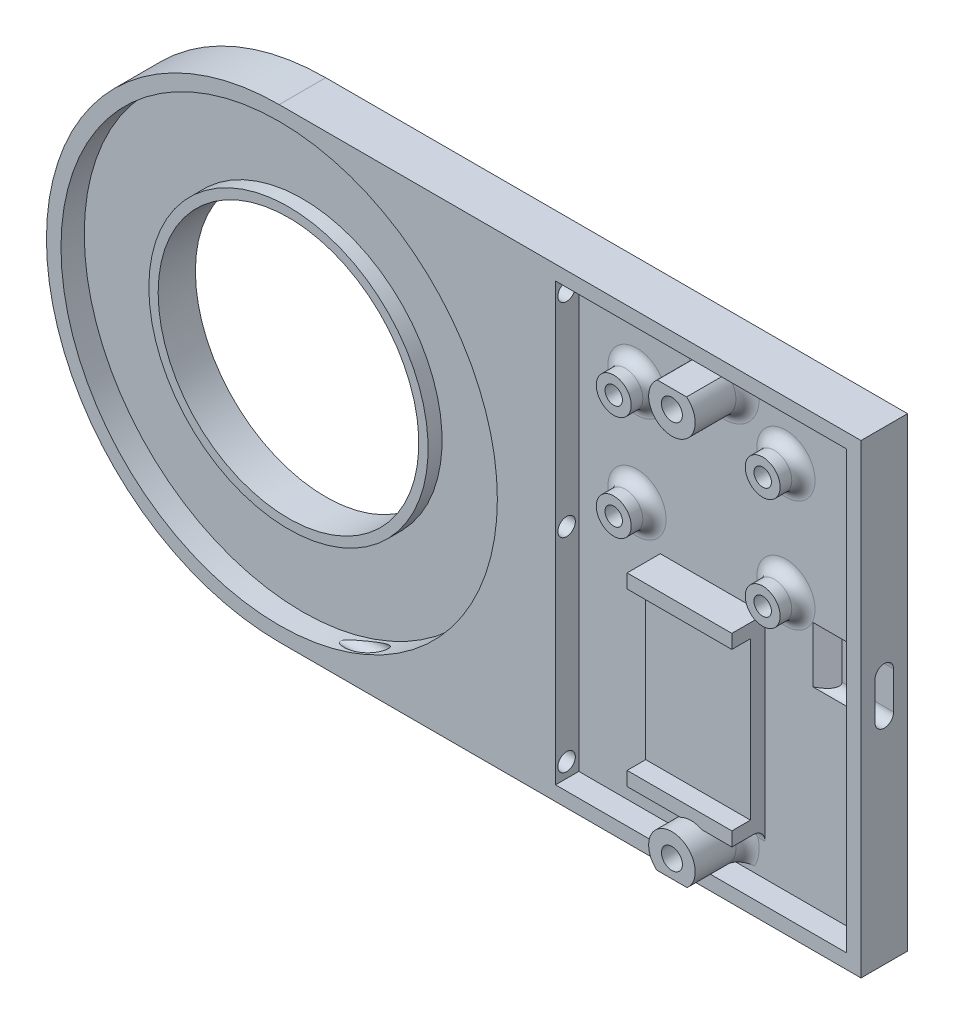
SolidWorks part; units mm, degrees
material "PET"
ref_plane "Front Plane" through (0, 0, 0) normal (0, 0, 1) x (1, 0, 0)
ref_plane "Top Plane" through (0, 0, 0) normal (0, 1, 0) x (1, 0, 0)
ref_plane "Right Plane" through (0, 0, 0) normal (1, 0, 0) x (0, 0, -1)
sketch "Sketch1" plane through (0, 0, 0) normal (0, 0, 1) x (1, 0, 0)
  line L0 (0, 25.4) -> (63.5, 25.4)
  line L1 (63.5, 25.4) -> (63.5, -25.4)
  line L2 (63.5, -25.4) -> (0, -25.4)
  circle A0 centre (0, 0) radius 15.24
  arc A1 (0, 25.4) -> (0, -25.4) centre (0, 0) ccw
  dimension "D1" = 30.48
  dimension "D2" = 25.4
  dimension "D3" = 63.5
extrude "Boss-Extrude1" add sketch "Sketch1" along normal blind 2.54
sketch "Sketch2" plane through (0, 0, 2.54) normal (0, 0, 1) x (1, 0, 0)
  line L3 (63.5, -25.4) -> (63.5, 25.4) construction
  line L4 (0, -25.4) -> (63.5, -25.4) construction
  line L5 (63.5, 25.4) -> (0, 25.4) construction
  line L6 (0, -23.8125) -> (61.9125, -23.8125)
  line L7 (61.9125, -23.8125) -> (61.9125, 23.8125)
  line L8 (61.9125, 23.8125) -> (0, 23.8125)
  line L9 (0, -23.8125) -> (61.9125, -23.8125)
  line L10 (61.9125, -23.8125) -> (61.9125, 23.8125)
  line L11 (61.9125, 23.8125) -> (0, 23.8125)
  line L12 (63.5, -25.4) -> (63.5, 25.4)
  line L13 (0, -25.4) -> (63.5, -25.4)
  line L14 (63.5, 25.4) -> (0, 25.4)
  arc A1 (0, 25.4) -> (0, -25.4) centre (0, 0) ccw construction
  arc A2 (0, 23.8125) -> (0, -23.8125) centre (0, 0) ccw
  arc A3 (0, 23.8125) -> (0, -23.8125) centre (0, 0) ccw
  arc A4 (0, 25.4) -> (0, -25.4) centre (0, 0) ccw
  dimension "D1" = 1.5875
extrude "Boss-Extrude2" add sketch "Sketch2" along normal blind 2.54
sketch "Sketch3" plane through (0, 0, 2.54) normal (0, 0, 1) x (1, 0, 0)
  line L0 (61.9125, 23.8125) -> (0, 23.8125) construction
  line L2 (23.8125, 23.8125) -> (23.8125, -23.8125) construction
  line L4 (30.1625, 23.8125) -> (30.1625, -23.8125)
  line L5 (0, -23.8125) -> (61.9125, -23.8125) construction
  line L6 (23.8125, 0) -> (30.1625, 0) construction
  line L7 (0, -23.8125) -> (30.1625, -23.8125)
  line L8 (0, 23.8125) -> (30.1625, 23.8125)
  circle A1 centre (0, 0) radius 23.8125 construction
  arc A3 (0, -23.8125) -> (0, 23.8125) centre (0, 0) ccw
  dimension "D1" = 6.35
extrude "Boss-Extrude3" add sketch "Sketch3" along normal up to surface (2.54 mm away) contours L4 L7 A3 L8 up to face at (25.4, 0, 5.08)
sketch "Sketch4" plane through (30.1625, 0, 0) normal (1, 0, 0) x (0, 0, -1)
  line L0 (-3.8735, -22.225) -> (-3.8735, 0) construction
  line L1 (-3.8735, 0) -> (-3.8735, 22.225) construction
  line L3 (-5.08, -25.4) -> (0, -25.4) construction
  line L4 (-5.08, 25.4) -> (0, 25.4) construction
  line L5 (-5.08, 0) -> (-4.826, 0) construction
  line L6 (-5.08, -25.4) -> (-5.08, 25.4) construction
  circle A0 centre (-3.8735, 22.225) radius 0.9525
  circle A1 centre (-3.8735, 0) radius 0.9525
  circle A2 centre (-3.8735, -22.225) radius 0.9525
  dimension "D1" = 1.905
  dimension "D2" = 1.905
  dimension "D3" = 1.905
  dimension "D4" = 3.175
  dimension "D5" = 3.175
  dimension "D6" = 25.4
  dimension "D7" = 0.254
extrude "Cut-Extrude1" cut sketch "Sketch4" against normal blind 31.75
sketch "Sketch6" plane through (0, 0, 2.54) normal (0, 0, 1) x (1, 0, 0)
  line L1 (52.7685, 4.3815) -> (36.5125, 4.7625) construction
  line L2 (36.5125, 4.7625) -> (36.5125, 16.1925) construction
  line L3 (36.5125, 16.1925) -> (52.7685, 16.5735) construction
  line L4 (36.5125, 4.7625) -> (52.7685, 4.7625) construction
  line L5 (36.5125, 16.1925) -> (52.7685, 16.1925) construction
  line L6 (52.7685, 16.5735) -> (52.7685, 16.1925) construction
  line L7 (52.7685, 16.1925) -> (52.7685, 4.7625) construction
  line L8 (52.7685, 4.7625) -> (52.7685, 4.3815) construction
  line L10 (30.1625, 23.8125) -> (30.1625, -23.8125) construction
  line L11 (61.9125, 23.8125) -> (30.1625, 23.8125) construction
  point P2 (34.5631, 12.8057)
  dimension "D1" = 0.381
  dimension "D2" = 0.381
  dimension "D3" = 11.43
  dimension "D4" = 16.256
  dimension "D5" = 11.43
  dimension "D6" = 6.35
  dimension "D7" = 7.62
sketch "Sketch8" plane through (0, 0, 2.54) normal (0, 0, 1) x (1, 0, 0)
  circle A0 centre (52.7685, 4.3815) radius 1.905
  circle A1 centre (36.5125, 4.7625) radius 1.905
  circle A2 centre (36.5125, 16.1925) radius 1.905
  circle A3 centre (52.7685, 16.5735) radius 1.905
  point P12 (35.9588, 16.7098)
  point P13 (35.9588, 4.5178)
  point P15 (52.2148, 4.8988)
  point P16 (52.2148, 16.3288)
  dimension "D3" = 3.81
extrude "Boss-Extrude5" add sketch "Sketch8" along normal blind 2.54
sketch "Sketch9" plane through (0, 0, 5.08) normal (0, 0, 1) x (1, 0, 0)
  circle A0 centre (52.7685, 4.3815) radius 0.9525
  circle A1 centre (36.5125, 4.7625) radius 0.9525
  circle A2 centre (52.7685, 16.5735) radius 0.9525
  circle A3 centre (36.5125, 16.1925) radius 0.9525
  point P12 (52.7861, 16.571)
  point P13 (0, 0)
  point P18 (52.2148, 16.1931)
  dimension "D1" = 1.905
extrude "Cut-Extrude2" cut sketch "Sketch9" against normal blind 3.81
sketch "Sketch10" plane through (0, 0, 2.54) normal (0, 0, 1) x (1, 0, 0)
  line L0 (30.1625, -23.8125) -> (30.1625, -18.7325)
  line L1 (30.1625, 23.8125) -> (30.1625, -23.8125) construction
  line L2 (30.1625, -18.7325) -> (37.1475, -18.7325)
  line L3 (37.1475, -18.7325) -> (37.1475, -23.8125)
  line L4 (30.1625, -23.8125) -> (61.9125, -23.8125) construction
  line L5 (37.1475, -23.8125) -> (30.1625, -23.8125) construction
  line L6 (30.1625, -23.8125) -> (30.1625, -25.4)
  line L7 (47.3075, -23.8125) -> (54.2925, -23.8125) construction
  line L8 (47.3075, -23.8125) -> (47.3075, -18.7325)
  line L9 (47.3075, -18.7325) -> (54.2925, -18.7325)
  line L10 (54.2925, -23.8125) -> (54.2925, -18.7325)
  line L11 (0, -25.4) -> (63.5, -25.4) construction
  line L12 (30.1625, -25.4) -> (37.1475, -25.4)
  line L13 (37.1475, -25.4) -> (37.1475, -23.8125)
  line L14 (47.3075, -23.8125) -> (47.3075, -25.4)
  line L15 (47.3075, -25.4) -> (54.2925, -25.4)
  line L16 (54.2925, -25.4) -> (54.2925, -23.8125)
  dimension "D1" = 6.985
  dimension "D2" = 10.16
  dimension "D3" = 6.985
  dimension "D4" = 5.08
  dimension "D5" = 5.08
ref_plane "Plane1" through (0, 0, 3.8735) normal (0, 0, 1) x (1, 0, 0)
sketch "Sketch11" plane through (0, 0, 2.54) normal (0, 0, 1) x (1, 0, 0)
  line L0 (30.1625, -23.8125) -> (61.9125, -23.8125) construction
  line L1 (39.0525, -0.3175) -> (50.4825, -0.3175)
  line L2 (39.0525, -0.3175) -> (39.0525, -17.4625)
  line L3 (39.0525, -17.4625) -> (50.4825, -17.4625)
  line L4 (50.4825, -0.3175) -> (50.4825, -17.4625)
  line L5 (30.1625, 23.8125) -> (30.1625, -23.8125) construction
  dimension "D1" = 11.43
  dimension "D2" = 17.145
  dimension "D3" = 6.35
  dimension "D4" = 8.89
extrude "Boss-Extrude6" add sketch "Sketch11" along normal blind 1.5875 contours L1 L4 L3 L2
sketch "Sketch12" plane through (0, 0, 2.54) normal (0, 0, 1) x (1, 0, 0)
  line L1 (39.0525, -0.3175) -> (50.4825, -0.3175)
  line L2 (39.0525, -0.3175) -> (39.0525, 1.2065)
  line L3 (39.0525, 1.2065) -> (50.4825, 1.2065)
  line L4 (50.4825, -0.3175) -> (50.4825, 1.2065)
  line L5 (50.4825, -17.4625) -> (39.0525, -17.4625)
  line L6 (50.4825, -17.4625) -> (50.4825, -18.9865)
  line L7 (50.4825, -18.9865) -> (39.0525, -18.9865)
  line L8 (39.0525, -17.4625) -> (39.0525, -18.9865)
  point P10 (39.0525, -18.7325)
  point P12 (50.4825, -1.5875)
  dimension "D1" = 1.524
  dimension "D2" = 1.524
extrude "Boss-Extrude12" add sketch "Sketch12" along normal offset from surface (3.6195 mm away) 2.032 up to face at (44.7675, -8.89, 4.1275) offset beyond the face yes
sketch "Sketch13" plane through (0, 0, 2.54) normal (0, 0, 1) x (1, 0, 0)
  line L1 (46.0375, 23.8125) -> (46.0375, -23.8125) construction
  line L5 (61.9125, 23.8125) -> (30.1625, 23.8125) construction
  line L6 (30.1625, -23.8125) -> (61.9125, -23.8125) construction
  circle A0 centre (46.0375, 21.2044) radius 2.54
  circle A1 centre (46.0375, -21.2479) radius 2.54
  point P4 (46.0375, 21.2044)
  point P5 (46.0375, -21.2479)
  dimension "D1" = 5.08
  dimension "D5" = 5.08
extrude "Boss-Extrude13" add sketch "Sketch13" along normal blind 5.715 contours A0 | A1
sketch "Sketch14" plane through (0, 0, 8.255) normal (0, 0, 1) x (1, 0, 0)
  circle A0 centre (46.0375, -21.2479) radius 1.143
  circle A1 centre (46.0375, 21.2044) radius 1.143
  dimension "D1" = 2.286
  dimension "D2" = 2.286
extrude "Cut-Extrude3" cut sketch "Sketch14" against normal offset from surface (6.731 mm away) 1.524 up to face at (25.4, 0, 0)
sketch "Sketch15" plane through (63.5, 0, 0) normal (1, 0, 0) x (0, 0, -1)
  line L0 (-2.54, -2.032) -> (-2.54, 2.032) construction
  line L2 (-3.556, -2.032) -> (-3.556, 2.032)
  line L3 (-1.524, -2.032) -> (-1.524, 2.032)
  line L4 (0, 0) -> (-2.54, 0) construction
  arc A0 (-3.556, -2.032) -> (-1.524, -2.032) centre (-2.54, -2.032) ccw
  arc A1 (-1.524, 2.032) -> (-3.556, 2.032) centre (-2.54, 2.032) ccw
  circle A2 centre (-2.54, 0) radius 0.889 construction
  circle A3 centre (-2.54, -2.032) radius 0.889 construction
  circle A4 centre (-2.54, 2.032) radius 0.889 construction
  point P5 (-2.54, 0)
  point P15 (-2.0017, 1.9594)
  dimension "D3" = 1.778
  dimension "D1" = 2.032
  dimension "D2" = 4.064
  dimension "D4" = 2.54
extrude "Cut-Extrude4" cut sketch "Sketch15" against normal blind 5.08
chamfer "Chamfer1" distance 1.27 angle 65 1 edges at (58.42, 0, 2.54) first distance on face at (58.42, 0, 1.9268)
sketch "Sketch16" plane through (0, 0, 0) normal (0, 0, -1) x (-1, 0, 0)
  circle A0 centre (0, 0) radius 15.24
  circle A1 centre (0, 0) radius 15.24 construction
  circle A2 centre (0, 0) radius 14.224
  dimension "D1" = 1.016
extrude "Boss-Extrude14" add sketch "Sketch16" against normal offset from surface (4.064 mm away) 1.524 up to face at (23.8125, 0, 2.54) offset beyond the face yes
sketch "Sketch17" plane through (0, 0, 2.54) normal (0, 0, 1) x (1, 0, 0)
  line L0 (61.9125, -23.8125) -> (61.9125, 23.8125) construction
  line L1 (30.1625, 23.8125) -> (61.9125, 23.8125)
  line L2 (30.1625, 23.8125) -> (30.1625, 23.1775)
  line L3 (30.1625, 23.1775) -> (61.9125, 23.1775)
  line L4 (61.9125, 23.8125) -> (61.9125, 23.1775)
  line L5 (30.1625, 23.8125) -> (30.1625, -23.8125) construction
  line L6 (30.1625, -23.1775) -> (61.9125, -23.1775)
  line L7 (30.1625, -23.1775) -> (30.1625, -23.8125)
  line L8 (30.1625, -23.8125) -> (61.9125, -23.8125)
  line L9 (61.9125, -23.1775) -> (61.9125, -23.8125)
  dimension "D1" = 0.635
  dimension "D2" = 0.635
extrude "Cut-Extrude5" cut sketch "Sketch17" along normal up to surface (5.715 mm away) up to face at (47.1805, 21.2044, 8.255)
fillet "Fillet1" radius 1.27 9 edges at (38.4175, 4.7625, 2.54) (38.4175, 16.1925, 2.54) (54.6735, 16.5735, 2.54) (54.6735, 4.3815, 2.54) (41.9667, -18.9865, 2.54) (43.515, -20.9499, 2.54) (48.8383, -18.9865, 2.54) (48.56, -20.9499, 2.54) (46.0375, 18.6644, 2.54)
